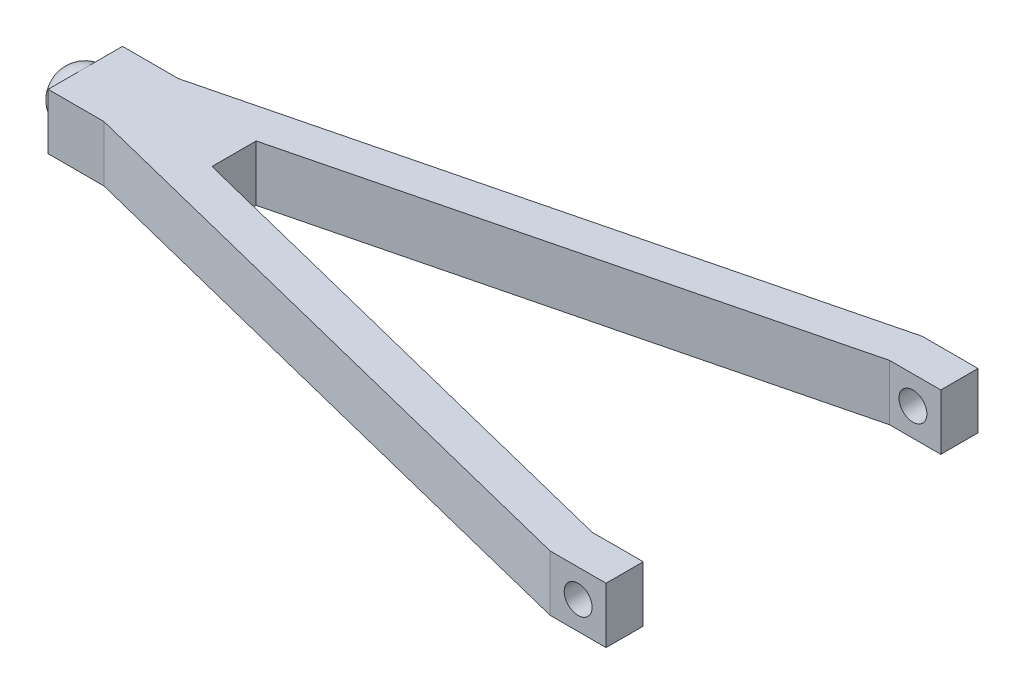
SolidWorks part; units mm, degrees
ref_plane "Front Plane" through (0, 0, 0) normal (0, 0, 1) x (1, 0, 0)
ref_plane "Top Plane" through (0, 0, 0) normal (0, 1, 0) x (1, 0, 0)
ref_plane "Right Plane" through (0, 0, 0) normal (1, 0, 0) x (0, 0, -1)
sketch "Sketch1" plane through (0, 0, 0) normal (0, 1, 0) x (1, 0, 0)
  line L0 (-38.1, 127) -> (-444.5, 25.4)
  line L1 (-444.5, 25.4) -> (-482.6, 25.4)
  line L2 (-482.6, 25.4) -> (-482.6, -25.4)
  line L3 (-38.1, 127) -> (0, 127)
  line L4 (0, 127) -> (0, 101.6)
  line L5 (0, 101.6) -> (-34.9731, 101.6)
  line L6 (-34.9731, 101.6) -> (-381, 15.0933)
  line L7 (-381, 15.0933) -> (-381, -15.0933)
  line L8 (-482.6, 0) -> (0, 0) construction
  line L9 (-34.9731, -101.6) -> (-381, -15.0933)
  line L10 (0, -101.6) -> (-34.9731, -101.6)
  line L11 (0, -127) -> (0, -101.6)
  line L12 (-38.1, -127) -> (0, -127)
  line L13 (-444.5, -25.4) -> (-482.6, -25.4)
  line L14 (-38.1, -127) -> (-444.5, -25.4)
  point P12 (-381, 0)
  point P18 (-404.6838, 49.427)
  point P19 (-359.3757, 16.9905)
  dimension "D1" = 38.1
  dimension "D2" = 25.4
  dimension "D3" = 25.4
  dimension "D4" = 406.4
  dimension "D5" = 50.8
  dimension "D6" = 101.6
  dimension "D7" = 254
  dimension "D8" = 38.1
extrude "Boss-Extrude1" add sketch "Sketch1" along normal blind 38.1
sketch "Sketch2" plane through (0, 0, 0) normal (0, 0, 1) x (1, 0, 0)
  line L0 (-482.6, 38.1) -> (-482.6, 0) construction
  line L1 (-482.6, 38.1) -> (-482.6, 0)
  arc A0 (-482.6, 38.1) -> (-482.6, 0) centre (-482.6, 19.05) ccw
revolve "Revolve1" add sketch "Sketch2" angle 360 about L1 region at (-490.6851, 19.05, 0)
sketch "Sketch3" plane through (0, 0, 127) normal (0, 0, 1) x (1, 0, 0)
  line L0 (0, 38.1) -> (-38.1, 0) construction
  circle A0 centre (-19.05, 19.05) radius 9.525
  dimension "D1" = 19.05
extrude "Cut-Extrude1" cut sketch "Sketch3" against normal through all both and the other way through all
